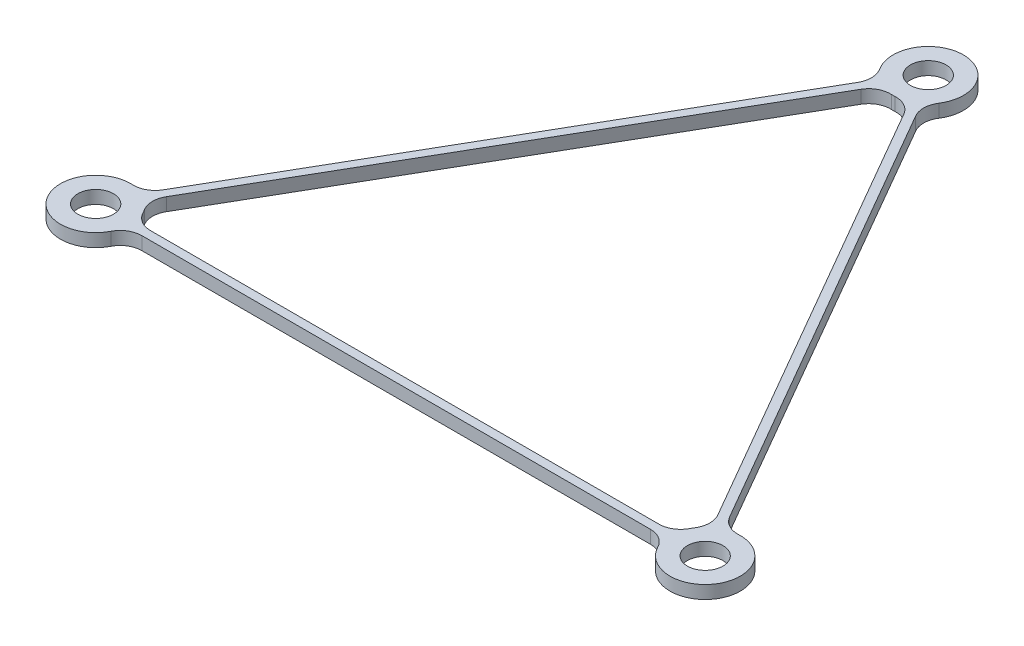
SolidWorks part; units mm, degrees
other "Markup1"
sketch "Sketch1" plane through (0, 0, 0) normal (0.4, 0.515, 0.7581) x (0.8844, 0, -0.4667)
ref_plane "Front Plane" through (0, 0, 0) normal (0, 0, 1) x (1, 0, 0)
ref_plane "Top Plane" through (0, 0, 0) normal (0, 1, 0) x (1, 0, 0)
ref_plane "Right Plane" through (0, 0, 0) normal (1, 0, 0) x (0, 0, -1)
sketch "Sketch2" plane through (0, 0, 0) normal (0, 1, 0) x (1, 0, 0)
  line L0 (35.1, -20.265) -> (0, 0) construction
  line L1 (0, 0) -> (0, 40.53) construction
  line L2 (0, 0) -> (-35.1, -20.265) construction
  line L3 (35.1, -20.265) -> (-35.1, -20.265) construction
  line L4 (-35.1, -20.265) -> (0, 40.53) construction
  line L5 (0, 40.53) -> (35.1, -20.265) construction
  line L6 (-33.5235, -16.5344) -> (-2.4425, 37.2994)
  line L7 (33.5235, -16.5344) -> (2.4425, 37.2994)
  line L8 (31.081, -20.765) -> (-31.081, -20.765)
  line L9 (-31.081, -19.765) -> (31.081, -19.765)
  line L10 (32.6575, -17.0344) -> (1.5765, 36.7994)
  line L11 (-1.5765, 36.7994) -> (-32.6575, -17.0344)
  line L12 (-17.983, 10.3825) -> (-17.117, 9.8825) construction
  line L13 (0, -20.765) -> (0, -19.765) construction
  line L14 (17.983, 10.3825) -> (17.117, 9.8825) construction
  circle A0 centre (0, 40.53) radius 2.05
  circle A1 centre (35.1, -20.265) radius 2.05
  circle A2 centre (-35.1, -20.265) radius 2.05
  arc A3 (32.6575, -17.0344) -> (31.081, -19.765) centre (35.1, -20.265) ccw
  arc A4 (-31.081, -19.765) -> (-32.6575, -17.0344) centre (-35.1, -20.265) ccw
  arc A5 (2.4425, 37.2994) -> (-2.4425, 37.2994) centre (0, 40.53) ccw
  arc A6 (31.081, -20.765) -> (33.5235, -16.5344) centre (35.1, -20.265) ccw
  arc A7 (-33.5235, -16.5344) -> (-31.081, -20.765) centre (-35.1, -20.265) ccw
  arc A8 (-1.5765, 36.7994) -> (1.5765, 36.7994) centre (0, 40.53) ccw
  point P14 (17.55, 10.1325)
  point P21 (-17.55, 10.1325)
  point P23 (0, -20.265)
  dimension "D2" = 4.1
  dimension "D3" = 2
  dimension "D1" = 70.2
  dimension "D4" = 1
extrude "main_shape" add sketch "Sketch2" along normal mid plane 1.5
fillet "outside_fillet" radius 2.5 6 edges at (-2.4425, 0, -37.2994) (2.4425, 0, -37.2994) (33.5235, 0, 16.5344) (31.081, 0, 20.765) (-31.081, 0, 20.765) (-33.5235, 0, 16.5344)
fillet "inside_fillet" radius 2.5 6 edges at (-32.6575, 0, 17.0344) (-31.081, 0, 19.765) (31.081, 0, 19.765) (32.6575, 0, 17.0344) (1.5765, 0, -36.7994) (-1.5765, 0, -36.7994)
